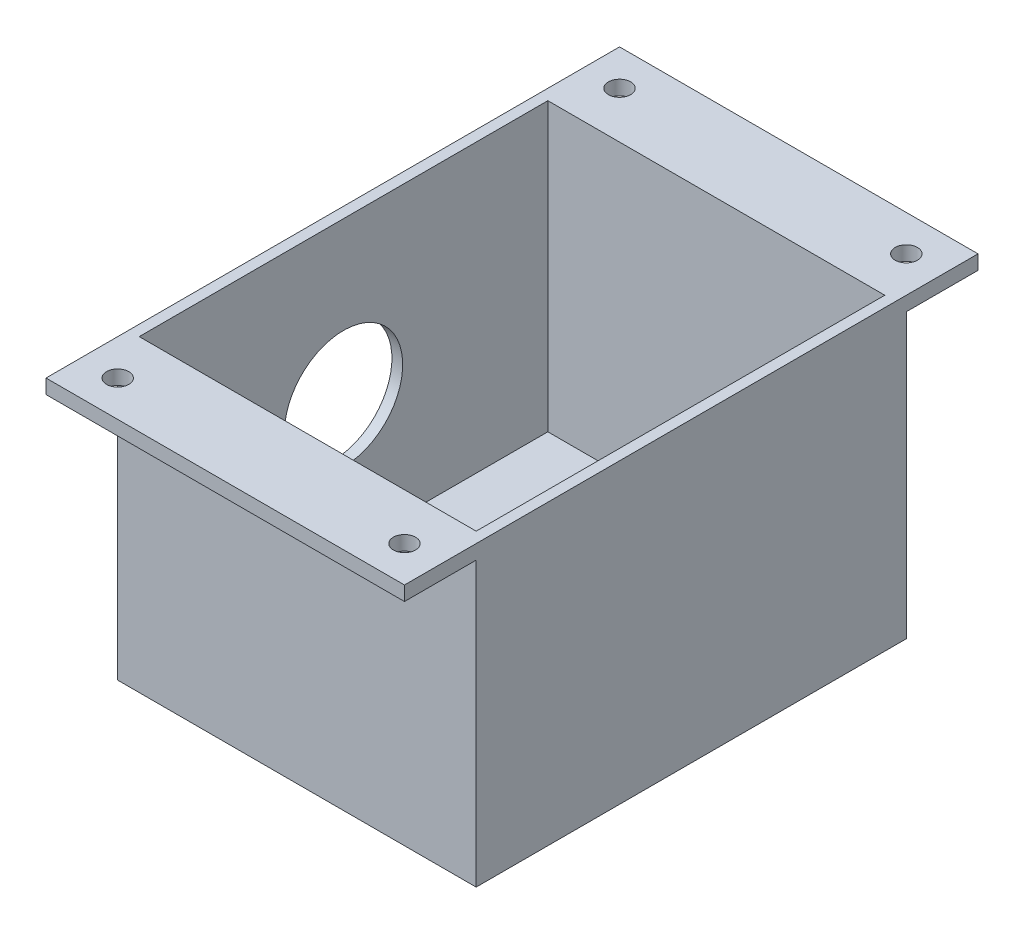
SolidWorks part; units mm, degrees
ref_plane "Płaszczyzna przednia" through (0, 0, 0) normal (0, 0, 1) x (1, 0, 0)
ref_plane "Płaszczyzna górna" through (0, 0, 0) normal (0, 1, 0) x (1, 0, 0)
ref_plane "Płaszczyzna prawa" through (0, 0, 0) normal (1, 0, 0) x (0, 0, -1)
sketch "Sketch1" plane through (0, 0, 0) normal (0, 1, 0) x (1, 0, 0)
  line L9 (-25, -40) -> (25, -40)
  line L16 (-25, -40) -> (-25, 40)
  line L21 (-25, 40) -> (25, 40)
  line L23 (25, -40) -> (25, 40)
  line L24 (-23.5, -28.5) -> (23.5, -28.5)
  line L25 (-23.5, -28.5) -> (-23.5, 28.5)
  line L26 (-25, -30) -> (25, -30)
  line L27 (-25, -30) -> (-25, 30)
  line L28 (-25, 30) -> (25, 30)
  line L29 (25, -30) -> (25, 30)
  line L30 (-23.5, 28.5) -> (23.5, 28.5)
  line L31 (23.5, -28.5) -> (23.5, 28.5)
  line L32 (-23.5, -28.5) -> (23.5, 28.5) construction
  line L33 (-23.5, 28.5) -> (23.5, -28.5) construction
  point P0 (0, 0)
  point P1 (0, 0)
  point P5 (0, 0)
  point P8 (0, 0)
  point P11 (0, 0)
  point P14 (0, 0)
  dimension "D1" = 50
  dimension "D2" = 80
  dimension "D3" = 50
  dimension "D4" = 60
  dimension "D5" = 47
  dimension "D6" = 57
extrude "Boss-Extrude6" add sketch "Sketch1" along normal blind 40 contours L28 L16 L26 L23 L31 L24 L25 L30 region at (-24.219, 0, 0)
sketch "Sketch7" plane through (0, 0, 0) normal (0, -1, 0) x (1, 0, 0)
  line L1 (-25, 30) -> (25, 30)
  line L2 (-25, 30) -> (-25, -30)
  line L3 (-25, -30) -> (25, -30)
  line L4 (25, 30) -> (25, -30)
extrude "Boss-Extrude8" add sketch "Sketch7" along normal blind 1.5
sketch "Sketch8" plane through (25, 0, 0) normal (1, 0, 0) x (0, 0, -1)
  line L1 (-30, 40) -> (-40, 40)
  line L2 (-30, 40) -> (-30, 38)
  line L3 (-30, 38) -> (-40, 38)
  line L4 (-40, 40) -> (-40, 38)
  line L5 (30, 40) -> (40, 40)
  line L6 (30, 40) -> (30, 38)
  line L7 (30, 38) -> (40, 38)
  line L8 (40, 40) -> (40, 38)
  dimension "D1" = 10
  dimension "D2" = 2
  dimension "D3" = 10
  dimension "D4" = 2
extrude "Boss-Extrude9" add sketch "Sketch8" against normal blind 50
sketch "Sketch9" plane through (0, 40, 0) normal (0, 1, 0) x (1, 0, 0)
  circle A0 centre (-20, 35) radius 1.55
  circle A1 centre (20, 35) radius 1.55
  circle A2 centre (20, -35) radius 1.55
  circle A3 centre (-20, -35) radius 1.55
  point P0 (0, 0)
  dimension "D1" = 40
  dimension "D2" = 70
extrude "Cut-Extrude1" cut sketch "Sketch9" against normal blind 3
sketch "Sketch11" plane through (-25, 0, 0) normal (-1, 0, 0) x (0, 0, 1)
  line L0 (-30, 18.25) -> (30, 18.25) construction
  line L1 (-30, 38) -> (-30, -1.5) construction
  line L2 (30, 38) -> (30, -1.5) construction
  line L4 (40, 40) -> (-40, 40) construction
  line L5 (0, 40) -> (0, -1.5) construction
  line L6 (30, -1.5) -> (-30, -1.5) construction
  circle A0 centre (0, 18.25) radius 8.25
  point P6 (0, 18.25)
extrude "Cut-Extrude3" cut sketch "Sketch11" against normal blind 1.5
